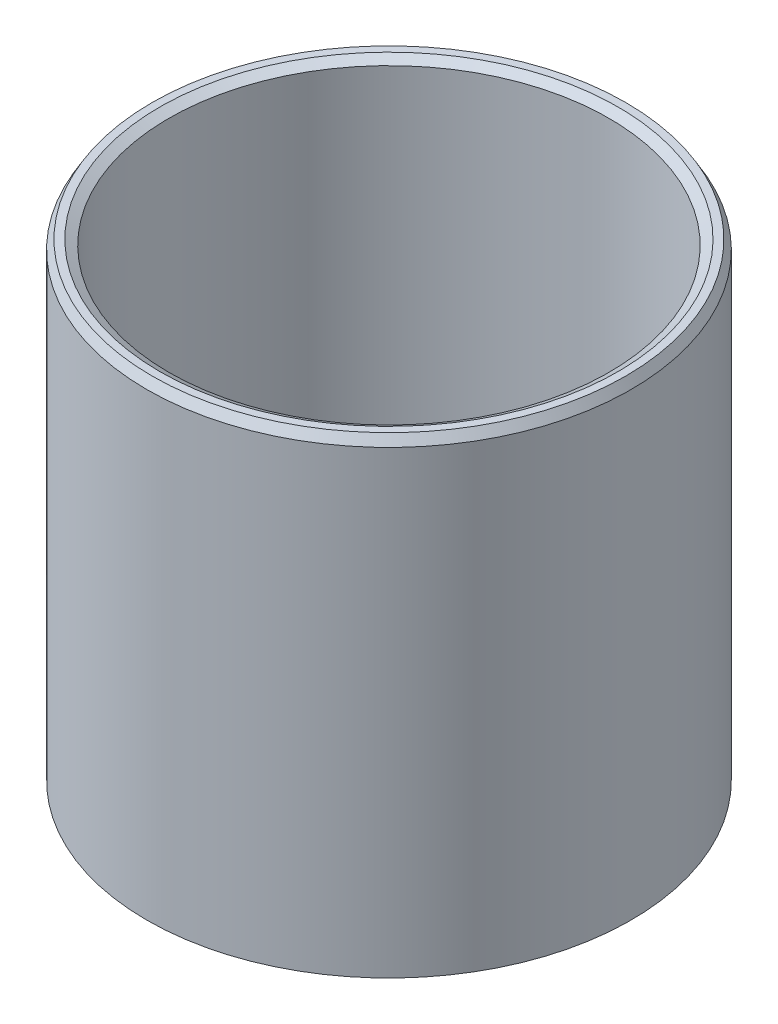
SolidWorks part; units mm, degrees
ref_plane "Front Plane" through (0, 0, 0) normal (0, 0, 1) x (1, 0, 0)
ref_plane "Top Plane" through (0, 0, 0) normal (0, 1, 0) x (1, 0, 0)
ref_plane "Right Plane" through (0, 0, 0) normal (1, 0, 0) x (0, 0, -1)
sketch "Sketch1" plane through (0, 0, 0) normal (0, 1, 0) x (1, 0, 0)
  circle A0 centre (0, 0) radius 55
  dimension "SLEEVE_OD" = 110
extrude "Boss-Extrude1" add sketch "Sketch1" along normal blind 107.6403
sketch "Sketch2" plane through (0, 0, 0) normal (0, 1, 0) x (1, 0, 0)
  circle A0 centre (0, 0) radius 49.9957
  dimension "BORE_D" = 99.9913
extrude "Cut-Extrude1" cut sketch "Sketch2" along normal through all
chamfer "Chamfer1" distance 2.0636 angle 30 4 edges at (0, 107.6403, 49.9957) (0, 0, 49.9957) (0, 0, 55) (0, 107.6403, 55) first distance on face at (0, 107.6403, 49.9957) first distance on face at (0, 0, 49.9957) first distance on face at (0, 107.6403, 55)
